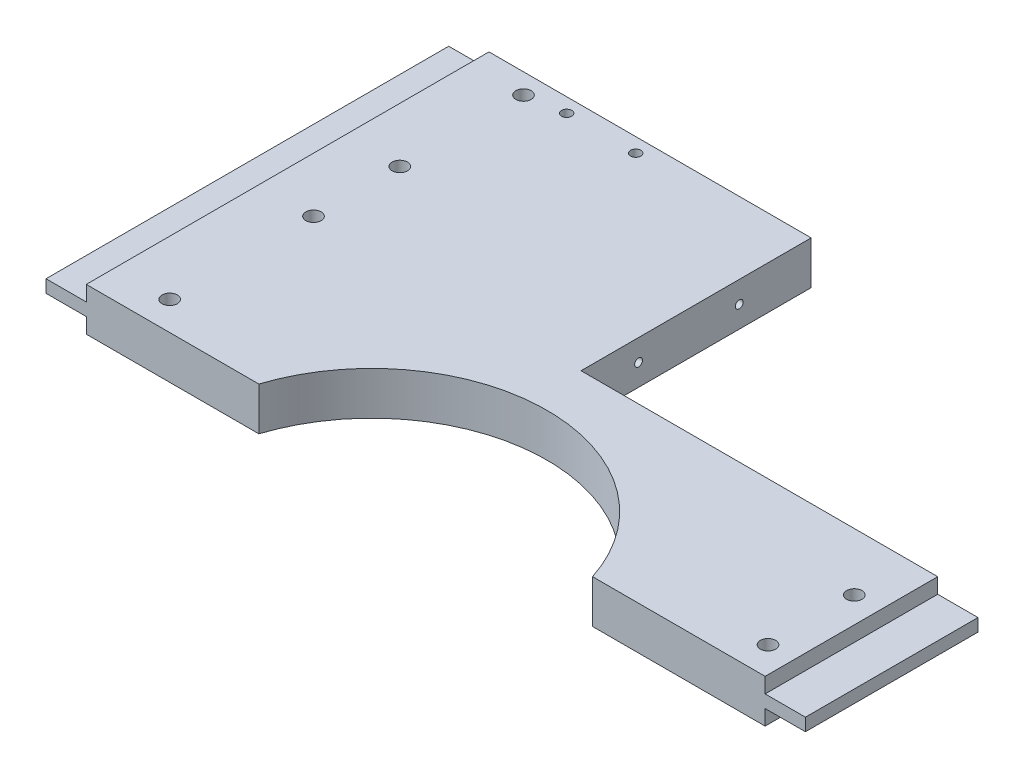
SolidWorks part; units mm, degrees
ref_plane "Front" through (0, 0, 0) normal (0, 0, 1) x (1, 0, 0)
ref_plane "Top" through (0, 0, 0) normal (0, 1, 0) x (1, 0, 0)
ref_plane "Right" through (0, 0, 0) normal (1, 0, 0) x (0, 0, -1)
sketch "Sketch1" plane through (0, 0, 0) normal (0, 1, 0) x (1, 0, 0)
  line L0 (-142.24, 101.6) -> (-142.24, -76.2)
  line L1 (-142.24, -76.2) -> (-66.04, -76.2)
  line L2 (-142.24, 101.6) -> (0, 101.6)
  line L3 (0, 101.6) -> (0, 0)
  line L4 (0, 0) -> (157.48, 0)
  line L5 (157.48, 0) -> (157.48, -76.2)
  line L6 (157.48, -76.2) -> (81.28, -76.2)
  circle A0 centre (7.62, -100.0615) radius 77.4285
  point P10 (7.62, -86.358)
  point P11 (7.62, -100.0615)
  dimension "D1" = 76.2
  dimension "D2" = 76.2
  dimension "D3" = 76.2
  dimension "D4" = 142.24
  dimension "D5" = 101.6
  dimension "D6" = 299.72
extrude "Boss-Extrude1" add sketch "Sketch1" along normal mid plane 19.05 contours A0 L6 L5 L4 L3 L2 L0 L1 region at (-28.4943, 0, -5.5871)
sketch "Sketch2" plane through (0, 0, 0) normal (0, 1, 0) x (1, 0, 0)
  line L0 (-142.24, -76.2) -> (-66.04, -76.2) construction
  line L1 (-142.24, 101.6) -> (-160.02, 101.6)
  line L2 (-142.24, 101.6) -> (-142.24, -76.2)
  line L3 (-142.24, -76.2) -> (-160.02, -76.2)
  line L4 (-160.02, 101.6) -> (-160.02, -76.2)
  line L5 (157.48, 0) -> (175.26, 0)
  line L6 (157.48, 0) -> (157.48, -76.2)
  line L7 (157.48, -76.2) -> (175.26, -76.2)
  line L8 (175.26, 0) -> (175.26, -76.2)
  line L9 (157.48, -76.2) -> (81.28, -76.2) construction
  dimension "D1" = 17.78
  dimension "D2" = 17.78
extrude "Boss-Extrude2" add sketch "Sketch2" along normal mid plane 5.588
sketch "Sketch3" plane through (0, 9.525, 0) normal (0, 1, 0) x (1, 0, 0)
  line L0 (-118.11, 101.6) -> (-118.11, -76.2) construction
  line L1 (-142.24, 101.6) -> (0, 101.6) construction
  line L2 (-142.24, -76.2) -> (-66.04, -76.2) construction
  line L3 (-142.24, -76.2) -> (-142.24, 101.6) construction
  line L4 (-142.24, 101.6) -> (-142.24, -76.2) construction
  line L5 (-142.24, 95.25) -> (0, 95.25) construction
  line L6 (0, 101.6) -> (0, 0) construction
  line L7 (146.05, 0) -> (146.05, -76.2) construction
  line L8 (0, 0) -> (157.48, 0) construction
  line L9 (157.48, -76.2) -> (81.28, -76.2) construction
  line L10 (157.48, 0) -> (157.48, -76.2) construction
  point P8 (-101.6, 95.25)
  point P9 (-71.12, 95.25)
  point P16 (-118.11, 0)
  point P17 (-118.11, 38.1)
  point P18 (-118.11, -63.5)
  point P19 (-118.11, 92.71)
  point P28 (146.05, -25.4)
  point P29 (146.05, -63.5)
  dimension "D1" = 24.13
  dimension "D2" = 40.64
  dimension "D3" = 71.12
  dimension "D4" = 8.89
  dimension "D5" = 12.7
  dimension "D6" = 76.2
  dimension "D7" = 114.3
  dimension "D8" = 6.35
  dimension "D9" = 11.43
  dimension "D10" = 12.7
  dimension "D11" = 25.4
hole_wizard "1/4 Clearance Hole1" positions "Sketch4" profile "Sketch6" hole size "1/4" standard "ANSI Inch" end condition through all
sketch "Sketch4" plane through (0, 9.525, 0) normal (0, 1, 0) x (1, 0, 0)
  point P0 (-118.11, 92.71)
  point P3 (-118.11, 38.1)
  point P6 (-118.11, 0)
  point P9 (-118.11, -63.5)
sketch "Sketch6" plane through (-118.11, 9.525, -92.71) normal (1, 0, 0) x (0, 0, 1)
  line L0 (0, 0) -> (0, 19.05)
  line L1 (0, 19.05) -> (3.3782, 19.05)
  line L2 (3.3782, 19.05) -> (3.3782, 0)
  line L5 (3.3782, 0) -> (0, 0)
  line L11 (0, -6.35) -> (0, 107.95) construction
  dimension "Thru Hole Dia." = 6.7564
  dimension "Thru Hole Depth" = 19.05
hole_wizard "#8 Clearance Hole1" positions "Sketch9" profile "Sketch10" hole size "#8" standard "ANSI Inch" end condition through all
sketch "Sketch9" plane through (0, 9.525, 0) normal (0, 1, 0) x (1, 0, 0)
  point P0 (-101.6, 95.25)
  point P3 (-71.12, 95.25)
sketch "Sketch10" plane through (-101.6, 9.525, -95.25) normal (1, 0, 0) x (0, 0, 1)
  line L0 (0, 0) -> (0, 19.05)
  line L1 (0, 19.05) -> (2.2479, 19.05)
  line L2 (2.2479, 19.05) -> (2.2479, 0)
  line L5 (2.2479, 0) -> (0, 0)
  line L11 (0, -6.35) -> (0, 107.95) construction
  dimension "Thru Hole Dia." = 4.4958
  dimension "Thru Hole Depth" = 19.05
hole_wizard "1/4 Clearance Hole2" positions "Sketch11" profile "Sketch12" hole size "1/4" standard "ANSI Inch" end condition through all
sketch "Sketch11" plane through (0, 9.525, 0) normal (0, 1, 0) x (1, 0, 0)
  point P0 (146.05, -25.4)
  point P3 (146.05, -63.5)
sketch "Sketch12" plane through (146.05, 9.525, 25.4) normal (1, 0, 0) x (0, 0, 1)
  line L0 (0, 0) -> (0, 19.05)
  line L1 (0, 19.05) -> (3.3782, 19.05)
  line L2 (3.3782, 19.05) -> (3.3782, 0)
  line L5 (3.3782, 0) -> (0, 0)
  line L11 (0, -6.35) -> (0, 107.95) construction
  dimension "Thru Hole Dia." = 6.7564
  dimension "Thru Hole Depth" = 19.05
sketch "Sketch13" plane through (0, 0, 0) normal (0, 0, -1) x (-1, 0, 0)
  line L0 (50, 0) -> (-50, 0) construction
  line L1 (-157.48, 9.525) -> (-157.48, 2.794) construction
  line L2 (0, 0) -> (-175.26, 0) construction
  line L3 (-175.26, 2.794) -> (-175.26, -2.794) construction
  point P0 (-137.16, 0)
  point P1 (-106.68, 0)
  point P2 (-55.88, 0)
  point P3 (-15.24, 0)
  dimension "D1" = 20.32
  dimension "D2" = 50.8
  dimension "D3" = 101.6
  dimension "D4" = 142.24
hole_wizard "#8-32 Tapped Hole1" positions "Sketch16" profile "Sketch18" tap size "#8-32" standard "ANSI Inch"
sketch "Sketch16" plane through (0, 0, 0) normal (0, 0, -1) x (-1, 0, 0)
  point P0 (-137.16, 0)
  point P3 (-106.68, 0)
  point P6 (-55.88, 0)
  point P9 (-15.24, 0)
sketch "Sketch18" plane through (137.16, 0, 0) normal (1, 0, 0) x (0, 1, 0)
  line L0 (0, 0) -> (0, 11.7058)
  line L1 (0, 11.7058) -> (1.7272, 10.668)
  line L2 (1.7272, 10.668) -> (1.7272, 0)
  line L5 (1.7272, 0) -> (0, 0)
  line L10 (0, 11.7058) -> (-1.7272, 10.668) construction
  line L11 (0, -6.35) -> (0, 107.95) construction
  dimension "Tap Drill Dia." = 3.4544
  dimension "Tap Drill Depth" = 10.668
  dimension "Drill Angle" = 118
cosmetic thread "Hole Thread1" parameters "D1"=8.382, "D2"=4.1656
cosmetic thread "Hole Thread2" parameters "D1"=8.382, "D2"=4.1656
cosmetic thread "Hole Thread3" parameters "D1"=8.382, "D2"=4.1656
cosmetic thread "Hole Thread4" parameters "D1"=8.382, "D2"=4.1656
sketch "Sketch19" plane through (0, 0, 0) normal (1, 0, 0) x (0, 0, -1)
  line L0 (0, 0) -> (101.6, 0) construction
  line L1 (101.6, 9.525) -> (101.6, -9.525) construction
  point P5 (69.85, 0)
  point P6 (25.4, 0)
  dimension "D1" = 31.75
  dimension "D2" = 76.2
hole_wizard "#8-32 Tapped Hole2" positions "Sketch21" profile "Sketch22" tap size "#8-32" standard "ANSI Inch"
sketch "Sketch21" plane through (0, 0, 0) normal (1, 0, 0) x (0, 0, -1)
  point P0 (69.85, 0)
  point P3 (25.4, 0)
sketch "Sketch22" plane through (0, 0, -69.85) normal (0, 1, 0) x (0, 0, -1)
  line L0 (0, 0) -> (0, 11.7058)
  line L1 (0, 11.7058) -> (1.7272, 10.668)
  line L2 (1.7272, 10.668) -> (1.7272, 0)
  line L5 (1.7272, 0) -> (0, 0)
  line L10 (0, 11.7058) -> (-1.7272, 10.668) construction
  line L11 (0, -6.35) -> (0, 107.95) construction
  dimension "Tap Drill Dia." = 3.4544
  dimension "Tap Drill Depth" = 10.668
  dimension "Drill Angle" = 118
cosmetic thread "Hole Thread5" parameters "D1"=8.382, "D2"=4.1656
cosmetic thread "Hole Thread6" parameters "D1"=8.382, "D2"=4.1656
